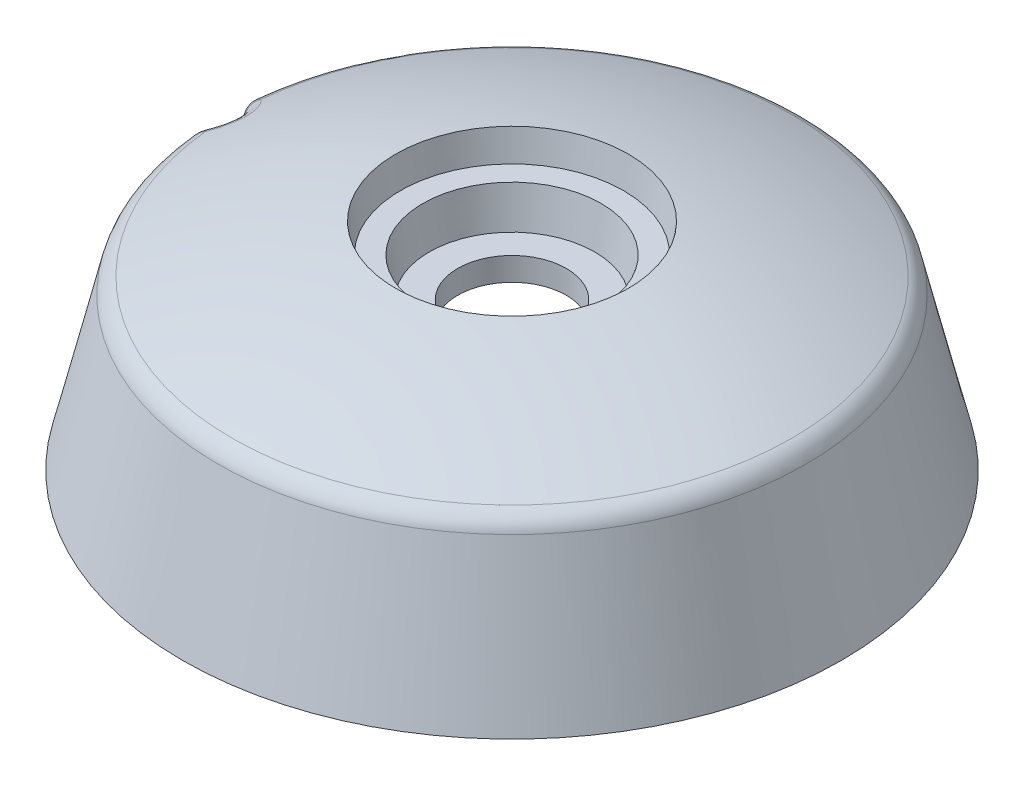
SolidWorks part; units mm, degrees
material "Plain Carbon Steel"
ref_plane "Front Plane" through (0, 0, 0) normal (0, 0, 1) x (1, 0, 0)
ref_plane "Top Plane" through (0, 0, 0) normal (0, 1, 0) x (1, 0, 0)
ref_plane "Right Plane" through (0, 0, 0) normal (1, 0, 0) x (0, 0, -1)
sketch "Sketch1" plane through (0, 0, 0) normal (0, 0, 1) x (1, 0, 0)
  line L0 (0, 0) -> (0, 36.4853) construction
  line L1 (-42.5, 0) -> (-37.5, 21)
  line L2 (-42.5, 0) -> (0, 0) construction
  line L3 (-15, 27.7675) -> (-14.3766, 24)
  line L4 (-14.3766, 24) -> (-11.5, 24)
  line L5 (-11.5, 24) -> (-10.6727, 19)
  line L6 (-10.6727, 19) -> (-7, 19)
  arc A0 (-37.5, 21) -> (-15, 27.7675) centre (0, -62.8906) cw
  dimension "D4" = 29
  dimension "D1" = 85
  dimension "D2" = 21
  dimension "D3" = 75
  dimension "D5" = 30
  dimension "D6" = 23
  dimension "D7" = 14
  dimension "D8" = 19
  dimension "D9" = 24
revolve "Revolve-Thin1" add sketch "Sketch1" angle 360 about L0
fillet "Fillet1" radius 3 1 edges at (0, 21, -37.5)
sketch "Sketch4" plane through (0, 0, 0) normal (0, 0, 1) x (1, 0, 0)
  line L0 (-37.8464, 19.5452) -> (-42.5, 0) construction
  line L1 (-36.2926, 30.3886) -> (-44.1143, -2.4628) construction
  line L2 (-39.1647, 5.3736) -> (-34.069, 26.7753)
  line L3 (-42.7779, 3.15) -> (-36.2926, 30.3886)
  line L4 (-42.7779, 3.15) -> (-60.6044, 7.3944) construction
  arc A0 (-42.7779, 3.15) -> (-39.1647, 5.3736) centre (-42.0831, 6.0685) ccw
  arc A1 (-36.2926, 30.3886) -> (-34.069, 26.7753) centre (-36.9874, 27.4702) cw
  dimension "D3" = 28
  dimension "D4" = 3
  dimension "D1" = 2
  dimension "D2" = 6
revolve "Cut-Revolve1" cut sketch "Sketch4" angle 360 about L1
fillet "Fillet2" radius 2 6 edges at (-41.7455, 3.1502, 0.608) (-39.1364, 13.7093, 2.7923) (-39.733, 11.2095, -2.7929) (-37.1656, 20.7367, 2.6605) (-36.8266, 21.1001, -2.5173) (-35.2286, 21.9783, -0.3185)
